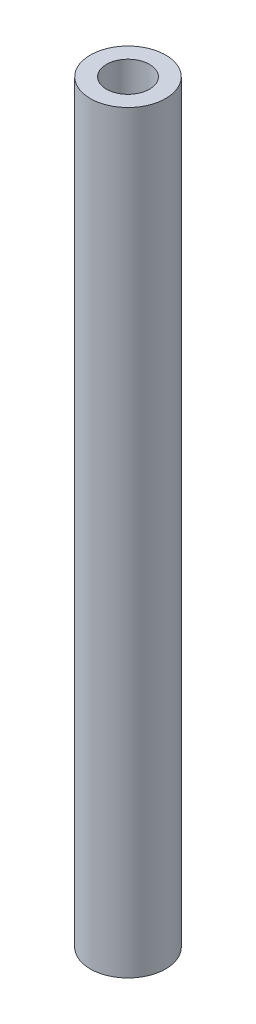
SolidWorks part; units mm, degrees
ref_plane "Front Plane" through (0, 0, 0) normal (0, 0, 1) x (1, 0, 0)
ref_plane "Top Plane" through (0, 0, 0) normal (0, 1, 0) x (1, 0, 0)
ref_plane "Right Plane" through (0, 0, 0) normal (1, 0, 0) x (0, 0, -1)
sketch "Sketch1" plane through (0, 0, 0) normal (0, 1, 0) x (1, 0, 0)
  circle A0 centre (0, 0) radius 1
  circle A1 centre (0, 0) radius 1.75
  dimension "D1" = 2
  dimension "D2" = 3.5
extrude "Boss-Extrude1" add sketch "Sketch1" along normal mid plane 35
